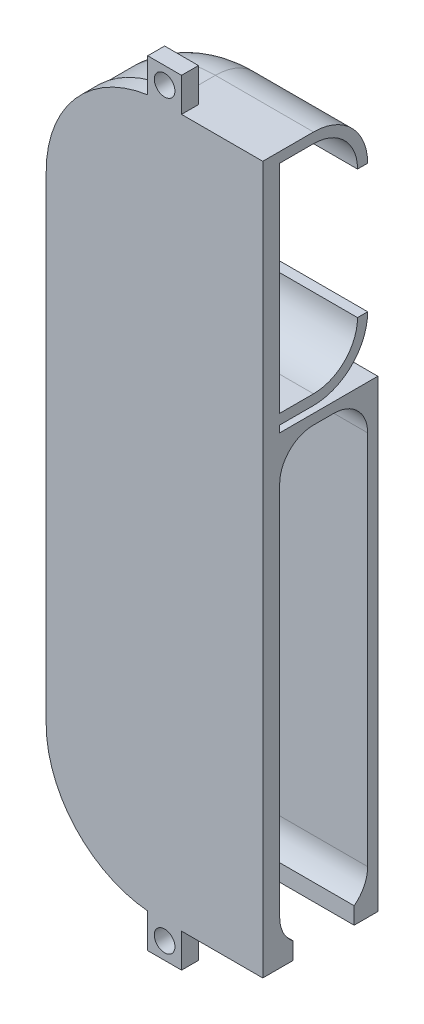
SolidWorks part; units mm, degrees
ref_plane "Front Plane" through (0, 0, 0) normal (0, 0, 1) x (1, 0, 0)
ref_plane "Top Plane" through (0, 0, 0) normal (0, 1, 0) x (1, 0, 0)
ref_plane "Right Plane" through (0, 0, 0) normal (1, 0, 0) x (0, 0, -1)
sketch "Sketch7" plane through (0, 0, 0) normal (0, 0, 1) x (1, 0, 0)
  line L0 (0, 29) -> (0, 26)
  line L1 (0, -26) -> (0, -29)
  arc A0 (0, -26) -> (0, 26) centre (0, 0) cw
  arc A1 (0, -29) -> (0, 29) centre (0, 0) cw
  dimension "D2" = 26
sketch "Sketch9" plane through (0, 0, 0) normal (0, 0, 1) x (1, 0, 0)
  line L0 (29, -7.5) -> (29, 7.5)
  line L1 (0, -26) -> (29, -26) construction
  line L2 (29, 7.5) -> (-10, 7.5)
  line L3 (-10, 7.5) -> (-10, -7.5)
  line L4 (-10, -7.5) -> (29, -7.5)
  line L5 (29, -26) -> (29, -7.5) construction
  line L7 (0, 26) -> (29, 26) construction
  line L8 (29, 26) -> (29, 7.5) construction
  arc A0 (-10, 7.5) -> (-10, -7.5) centre (-10, 0) ccw
  dimension "D4" = 15
  dimension "D1" = 15
  dimension "D2" = 39
  dimension "D3" = 29
sketch "r" plane through (0, 0, 0) normal (0, 0, 1) x (1, 0, 0)
  line L0 (29, -171) -> (-2, -171)
  line L1 (-32, -141) -> (-32, -40)
  line L2 (-32, -40) -> (29, -40)
  arc A0 (-2, -171) -> (-32, -141) centre (-2, -141) cw
  dimension "D1" = 30
  dimension "D2" = 31
  dimension "D3" = 61
  dimension "D4" = 101
  dimension "D5" = 40
  dimension "D6" = 29
ref_plane "Plane1" through (29, 0, 0) normal (1, 0, 0) x (0, 0, -1)
sketch "Sketch11" plane through (29, 0, 0) normal (1, 0, 0) x (0, 0, -1)
  line L0 (0, -171) -> (0, -174)
  line L1 (0, -141) -> (0, -171) construction
  line L2 (0, -174) -> (29, -174)
  line L3 (29, -174) -> (29, -152.0781)
  line L4 (29, -152.0781) -> (26, -152.0781)
  line L5 (26, -152.0781) -> (26, -171)
  line L6 (26, -171) -> (0, -171)
  dimension "D1" = 3
  dimension "D2" = 3
  dimension "D3" = 26
sweep "Sweep1" add profiles "Sketch11" path "r"
fillet "Fillet1" radius 10 4 edges at (-1.5, -40, -26) (-23.2132, -162.2132, -26) (13.5, -171, -26) (-32, -90.5, -26)
sketch "Sketch12" plane through (0, 0, 0) normal (0, 0, 1) x (1, 0, 0)
  line L0 (5, 35) -> (-5, 35) construction
  line L2 (29, 35) -> (29, -174)
  line L5 (-5, 45) -> (-5, 35)
  line L6 (29, -174) -> (-2, -174) construction
  line L8 (-5, 45) -> (5, 45)
  line L9 (5, 45) -> (5, 35)
  line L10 (5, -174) -> (5, -184)
  line L11 (5, -184) -> (-5, -184)
  line L15 (-5, -184) -> (-5, -173.8634)
  line L16 (5, -174) -> (29, -174)
  line L17 (29, 35) -> (5, 35)
  line L18 (-35, -141) -> (-35, 0)
  line L20 (29, -40) -> (29, -37) construction
  circle A4 centre (0, -179) radius 3.05
  circle A5 centre (0, 40) radius 3.05
  arc A8 (-35, -141) -> (-2, -174) centre (-2, -141) ccw construction
  arc A9 (-35, -141) -> (-5, -173.8634) centre (-2, -141) ccw
  arc A12 (-5, 35) -> (-35, 0) centre (-0.0018, 0.3587) ccw
  line M36 (-35, -37) -> (-32, -40)
  line M37 (-32, -40) -> (29, -40)
  line M38 (29, -40) -> (29, -37)
  line M39 (29, -37) -> (-35, -37)
  dimension "D8" = 6.1
  dimension "D9" = 5
  dimension "D10" = 5
  dimension "D11" = 6.1
  dimension "D13" = 5
  dimension "D16" = 35
  dimension "D2" = 10
  dimension "D3" = 24
  dimension "D4" = 10
  dimension "D5" = 10
  dimension "D6" = 10
  dimension "D7" = 24
  dimension "D12" = 5
  dimension "D14" = 209
extrude "Boss-Extrude4" add sketch "Sketch12" along normal blind 5 contours L18 L2 L17 L9 L8 A5 M39 | L18 A9 L15 L11 L10 L16 L2 A4 M37 M36 | M39 M36 M37 M38 | L0 L9 L8 L5 A5 region at (-1.5832, -2.6276, 0) region at (0, 35.1414, 0) region at (-2.256, -38.488, 0) region at (-2.3076, -105.9146, 0)
fillet "Fillet2" radius 10 4 edges at (13.5, -171, 0) (-23.2132, -162.2132, 0) (-32, -90.5, 0) (-1.5, -40, 0)
sketch "Sketch13" plane through (-35, 0, 0) normal (-1, 0, 0) x (0, 0, 1)
  line L1 (-22, -76.5) -> (-4, -76.5)
  line L2 (-22, -76.5) -> (-22, -176.5)
  line L3 (-22, -176.5) -> (-4, -176.5)
  line L4 (-4, -76.5) -> (-4, -176.5)
  line L5 (-29, -141) -> (-29, -37) construction
  line L6 (-29, -37) -> (0, -37) construction
  dimension "D1" = 100
  dimension "D2" = 18
  dimension "D3" = 25
  dimension "D4" = 39.5
extrude "Cut-Extrude5" cut sketch "Sketch13" against normal up to next
sketch "Sketch14" plane through (0, 0, 0) normal (1, 0, 0) x (0, 0, -1)
  line L0 (0, -26) -> (0, -29) construction
  line L1 (0, -35) -> (10, -35)
  line L2 (0, -35) -> (0, -32)
  line L3 (0, -32) -> (10, -32)
  line L5 (0, 29) -> (0, -29) construction
  line L6 (23, -19) -> (26, -19)
  line L7 (23, 0) -> (26, 0) construction
  arc A0 (10, -32) -> (23, -19) centre (10, -19) ccw
  arc A1 (10, -35) -> (26, -19) centre (10, -19) ccw
  dimension "D1" = 3
  dimension "D2" = 10
  dimension "D3" = 32
  dimension "D5" = 3
  dimension "D4" = 3
revolve "Revolve2" add sketch "Sketch14" angle 180 about L7 region at (0, -33.5, -0.3053)
extrude "Boss-Extrude5" add sketch "Sketch14<4>" along normal through all contours L1 A1 L7 A0 L3 L2 region at (0, -33.5, -0.3053)
sketch "Sketch14<4>" plane through (0, 0, 0) normal (1, 0, 0) x (0, 0, -1) same geometry as "Sketch14"
ref_plane "Plane3" through (0, 0, 0) normal (0, 1, 0) x (1, 0, 0)
mirror "Mirror1" about plane through (0, 0, 0) normal (0, 1, 0) of "Boss-Extrude5"
extrude "Cut-Extrude6" [suppressed] cut sketch "Sketch9" against normal through all contours L3 L4 L0 L2 | L3 A0
fillet "Fillet3" radius 9 1 edges at (-35, -37, -14.5)
sketch "Sketch15" plane through (0, 0, -29) normal (0, 0, -1) x (-1, 0, 0)
  line L0 (-29, 15.95) -> (-29, -15.95) construction
  line L1 (13.0781, -58.9219) -> (-29, -58.9219)
  line L2 (13.0781, -58.9219) -> (13.0781, -152.0781)
  line L3 (13.0781, -152.0781) -> (-29, -152.0781)
  line L4 (-29, -58.9219) -> (-29, -152.0781)
  line L5 (-29, -152.0781) -> (2, -152.0781) construction
  line L6 (35, -141) -> (35, -46) construction
  line L7 (13.0781, -76.5) -> (35, -76.5)
  line L8 (13.0781, -76.5) -> (13.0781, -127.5)
  line L9 (13.0781, -127.5) -> (35, -127.5)
  line L10 (35, -76.5) -> (35, -127.5)
  line M5 (-29, -58.9219) -> (13.0781, -58.9219)
extrude "Boss-Extrude6" add sketch "Sketch15" against normal blind 3 contours L4 L3 L2 M5 | L10 L7 L2 L9 region at (7.9609, -105.5, -29) region at (-24.0391, -102, -29)
